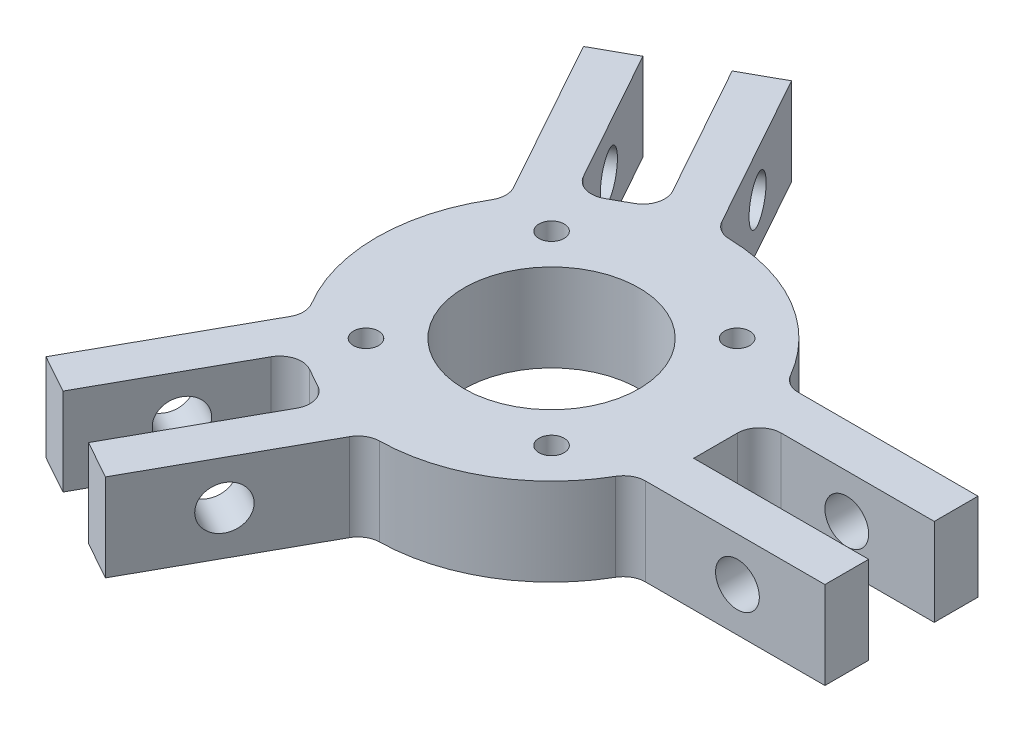
SolidWorks part; units mm, degrees
material "6061 Alloy"
ref_plane "Front Plane" through (0, 0, 0) normal (0, 0, 1) x (1, 0, 0)
ref_plane "Top Plane" through (0, 0, 0) normal (0, 1, 0) x (1, 0, 0)
ref_plane "Right Plane" through (0, 0, 0) normal (1, 0, 0) x (0, 0, -1)
sketch3d "Planning"
  line L0 (0, 0, 0) -> (38.1, 0, 0) construction
  line L1 (38.1, 0, 0) -> (355.6, -190.5, 0) construction
  line L2 (355.6, -190.5, 0) -> (355.6, -203.2, 0) construction
  line L3 (0, 0, 0) -> (-18.503, 0, 33.3054) construction
  line L4 (0, 0, 0) -> (-18.503, 0, -33.3054) construction
  line L5 (-18.503, 0, 33.3054) -> (-127, -190.5, 228.6) construction
  line L6 (-127, -190.5, 228.6) -> (-127, -203.2, 228.6) construction
  line L7 (-18.503, 0, -33.3054) -> (-127, -190.5, -228.6) construction
  line L8 (-127, -190.5, -228.6) -> (-127, -203.2, -228.6) construction
  line L9 (-18.503, 0, -33.3054) -> (-18.503, 0, 33.3054) construction
  line L10 (-127, -203.2, -228.6) -> (-127, -203.2, 228.6) construction
  line L11 (355.6, -203.2, 0) -> (-127, -203.2, 0) construction
  line L12 (0, 0, 0) -> (0, -203.2, 0) construction
  point P11 (-18.503, 0, 0)
  dimension "D1" = 38.1
  dimension "D2" = 12.7
  dimension "D3" = 203.2
  dimension "D4" = 482.6
  dimension "D5" = 127
  dimension "D6" = 457.2
sketch "Sketch1" plane through (0, 0, 0) normal (0, 1, 0) x (1, 0, 0)
  line L0 (0, 0) -> (25.4, 0) construction
  line L1 (25.4, 4.7625) -> (25.4, -4.7625)
  line L2 (25.4, -4.7625) -> (50.8, -4.7625)
  line L3 (50.8, -4.7625) -> (50.8, -11.1125)
  line L4 (25.4, 4.7625) -> (50.8, 4.7625)
  line L5 (13.4704, 13.4704) -> (-13.4704, -13.4704) construction
  line L6 (13.4704, -13.4704) -> (-13.4704, 13.4704) construction
  line L7 (50.8, 4.7625) -> (50.8, 11.1125)
  line L8 (0, 0) -> (-12.3353, -22.2036) construction
  line L9 (38.1, 4.7625) -> (38.1, -4.7625) construction
  line L10 (-34.3847, -39.0105) -> (-28.8338, -42.0943)
  line L11 (-28.8338, -42.0943) -> (-16.4985, -19.8907)
  line L12 (-16.4985, -19.8907) -> (-8.1722, -24.5165)
  line L13 (-8.1722, -24.5165) -> (-20.5075, -46.7201)
  line L14 (-20.5075, -46.7201) -> (-14.9566, -49.8039)
  line L15 (-14.9566, -49.8039) -> (-1.3781, -25.3626)
  line L16 (50.8, -11.1125) -> (22.8401, -11.1125)
  line L17 (-34.3847, -39.0105) -> (-20.8062, -14.5692)
  line L18 (0, 0) -> (-12.3353, 22.2036) construction
  line L19 (-14.9566, 49.8039) -> (-1.3781, 25.3626)
  line L20 (-20.5075, 46.7201) -> (-14.9566, 49.8039)
  line L21 (-8.1722, 24.5165) -> (-20.5075, 46.7201)
  line L22 (-16.4985, 19.8907) -> (-8.1722, 24.5165)
  line L23 (-28.8338, 42.0943) -> (-16.4985, 19.8907)
  line L24 (-34.3847, 39.0105) -> (-28.8338, 42.0943)
  line L25 (-34.3847, 39.0105) -> (-20.8062, 14.5692)
  line L26 (50.8, 11.1125) -> (22.8401, 11.1125)
  line L27 (0, 0) -> (-18.503, 33.3054) construction
  circle A0 centre (0, 0) radius 12.7
  circle A1 centre (-13.4704, 13.4704) radius 1.8288
  circle A2 centre (13.4704, 13.4704) radius 1.8288
  circle A3 centre (13.4704, -13.4704) radius 1.8288
  circle A4 centre (-13.4704, -13.4704) radius 1.8288
  arc A5 (-1.3781, -25.3626) -> (22.8401, -11.1125) centre (0, 0) ccw
  arc A6 (-1.3781, 25.3626) -> (22.8401, 11.1125) centre (0, 0) cw
  arc A7 (-20.8062, 14.5692) -> (-20.8062, -14.5692) centre (0, 0) ccw
  dimension "D3" = 25.4
  dimension "D5" = 3.6576
  dimension "D8" = 25.4
  dimension "D1" = 9.525
  dimension "D2" = 25.4
  dimension "D4" = 38.1
  dimension "D6" = 6.35
extrude "Boss-Extrude1" add sketch "Sketch1" along normal mid plane 12.7
hole_wizard "1/4 (0.25) Diameter Hole1" positions "3DSketch1" profile "Sketch4" hole size "1/4" standard "ANSI Inch" end condition up to next
sketch3d "3DSketch1"
  line L0 (25.4, -6.35, 4.7625) -> (50.8, 6.35, 4.7625) construction
  line L3 (25.4, -6.35, -4.7625) -> (50.8, 6.35, -4.7625) construction
  line L6 (-8.1722, -6.35, -24.5165) -> (-20.5075, 6.35, -46.7201) construction
  line L9 (-16.4985, -6.35, -19.8907) -> (-28.8338, 6.35, -42.0943) construction
  line L12 (-8.1722, -6.35, 24.5165) -> (-20.5075, 6.35, 46.7201) construction
  line L15 (-28.8338, 6.35, 42.0943) -> (-16.4985, -6.35, 19.8907) construction
  point P0 (38.1, 0, -4.7625)
  point P2 (-14.3398, 0, -35.6183)
  point P4 (-22.6662, 0, 30.9925)
  point P6 (-14.3398, 0, 35.6183)
  point P8 (-22.6662, 0, -30.9925)
  point P10 (38.1, 0, 4.7625)
sketch "Sketch4" plane through (38.1, 0, -4.7625) normal (1, 0, 0) x (0, -1, 0)
  line L0 (0, 0) -> (0, 6.35)
  line L1 (0, 6.35) -> (3.175, 6.35)
  line L2 (3.175, 6.35) -> (3.175, 0)
  line L5 (3.175, 0) -> (0, 0)
  line L11 (0, -6.35) -> (0, 107.95) construction
  dimension "Thru Hole Dia." = 6.35
  dimension "Thru Hole Depth" = 6.35
fillet "Fillet1" radius 3.175 11 edges at (-20.8062, 0, 14.5692) (-16.4985, 0, 19.8907) (-8.1722, 0, 24.5165) (-1.3781, 0, 25.3626) (22.8401, 0, 11.1125) (25.4, 0, -4.7625) (22.8401, 0, -11.1125) (-1.3781, 0, -25.3626) (-8.1722, 0, -24.5165) (-16.4985, 0, -19.8907) (-20.8062, 0, -14.5692)
